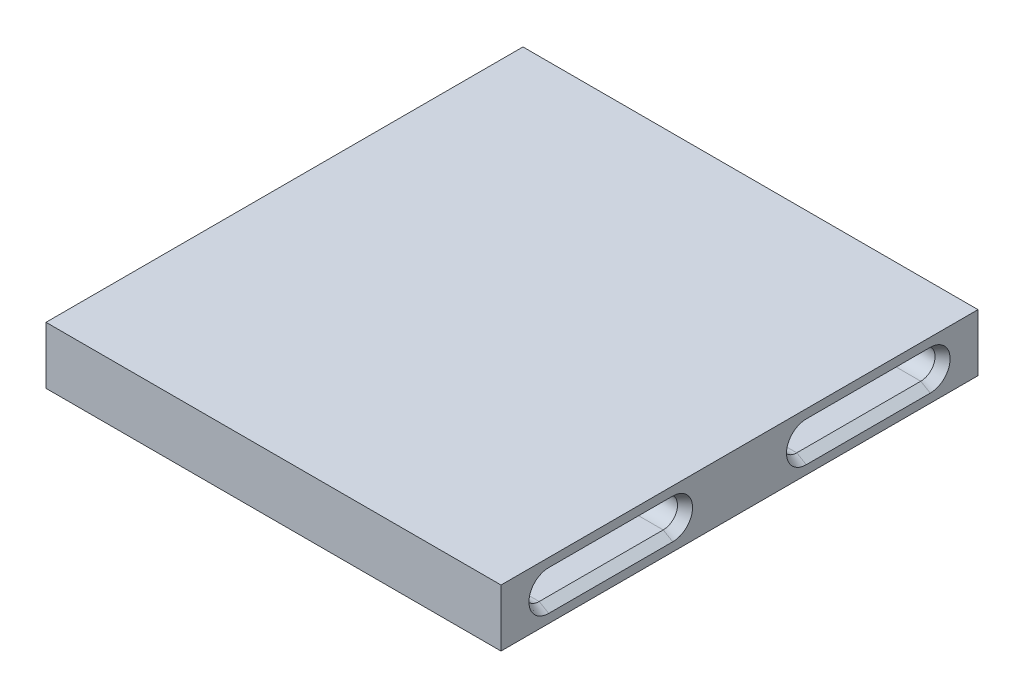
SolidWorks part; units mm, degrees
ref_plane "Front Plane" through (0, 0, 0) normal (0, 0, 1) x (1, 0, 0)
ref_plane "Top Plane" through (0, 0, 0) normal (0, 1, 0) x (1, 0, 0)
ref_plane "Right Plane" through (0, 0, 0) normal (1, 0, 0) x (0, 0, -1)
sketch "Sketch1" plane through (0, 0, 0) normal (1, 0, 0) x (0, 0, -1)
  line L1 (-12.5, -1.5) -> (12.5, -1.5)
  line L2 (-12.5, -1.5) -> (-12.5, 1.5)
  line L3 (-12.5, 1.5) -> (12.5, 1.5)
  line L4 (12.5, -1.5) -> (12.5, 1.5)
  line L5 (-12.5, -1.5) -> (12.5, 1.5) construction
  line L6 (-12.5, 1.5) -> (12.5, -1.5) construction
  point P0 (0, 0)
  dimension "D1" = 25
  dimension "D2" = 3
extrude "Boss-Extrude1" add sketch "Sketch1" along normal blind 23.85
sketch "Sketch2" plane through (0, 0, 0) normal (-1, 0, 0) x (0, 0, 1)
  line L5 (-10, 0) -> (-3.5, 0) construction
  line L6 (-10, 0.75) -> (-3.5, 0.75)
  line L11 (-10, -0.75) -> (-3.5, -0.75)
  line L12 (3.5, 0) -> (10, 0) construction
  line L13 (3.5, 0.75) -> (10, 0.75)
  line L14 (3.5, -0.75) -> (10, -0.75)
  arc A0 (-10, 0.75) -> (-10, -0.75) centre (-10, 0) ccw
  arc A1 (-3.5, -0.75) -> (-3.5, 0.75) centre (-3.5, 0) ccw
  arc A2 (3.5, 0.75) -> (3.5, -0.75) centre (3.5, 0) ccw
  arc A3 (10, -0.75) -> (10, 0.75) centre (10, 0) ccw
  point P2 (-6.75, 0)
  point P7 (6.75, 0)
  dimension "D3" = 0.75
  dimension "D4" = 0.75
  dimension "D1" = 6.5
  dimension "D2" = 6.5
  dimension "D5" = 7
  dimension "D6" = 3.5
extrude "Cut-Extrude1" cut sketch "Sketch2" against normal through all both and the other way through all
sketch "Sketch3" plane through (0, 0, 0) normal (-1, 0, 0) x (0, 0, 1)
  circle A0 centre (0, 0) radius 1.05
  dimension "D1" = 2.1
extrude "Cut-Extrude2" cut sketch "Sketch3" against normal blind 10
chamfer "Chamfer1" distance 0.5 angle 30 8 edges at (23.85, 0, -10.75) (23.85, -0.75, -6.75) (23.85, 0.75, -6.75) (23.85, 0, -2.75) (23.85, 0, 2.75) (23.85, -0.75, 6.75) (23.85, 0, 10.75) (23.85, 0.75, 6.75) first distance on face at (11.925, 0, -10.375) first distance on face at (11.925, -0.75, -6.75) first distance on face at (11.925, 0.75, -6.75) first distance on face at (11.925, 0, -3.125) first distance on face at (11.925, 0, 3.125) first distance on face at (11.925, -0.75, 6.75) first distance on face at (11.925, 0, 10.375) first distance on face at (11.925, 0.75, 6.75)
thread "Thread1" pitch 0.4 method cut profile "Thread Profile2" start angle 0, offset 0, length 0, pitch 0.4, diameter 2.1
ref_plane "Plane2" through (0, 0, -1.05) normal (0, -1, 0) x (0, 0, -1)
sketch "Thread Profile2" plane through (0, 0, -1.05) normal (0, -1, 0) x (0, 0, -1)
  line L0 (0, 0) -> (0, 0.4) construction
  line L1 (0, 0) -> (0.2165, 0.125)
  line L2 (0.2165, 0.125) -> (0.2165, 0.175)
  line L3 (0.2165, 0.175) -> (0, 0.3)
  line L4 (0.2165, 0.15) -> (0, 0.15) construction
  line L11 (0, 0) -> (0, 0.3)
  point P2 (0, 0)
  dimension "Pitch" = 0.4
  dimension "Profile_Angle" = 60
  dimension "Profile_Land" = 0.05
  dimension "Profile_Height" = 0.2165
